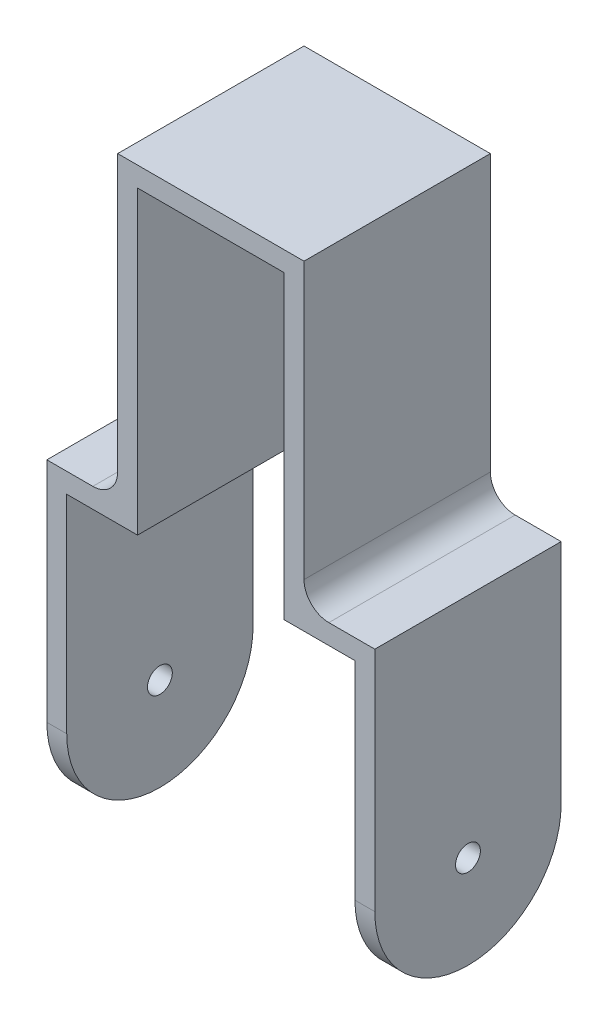
SolidWorks part; units mm, degrees
ref_plane "Front Plane" through (0, 0, 0) normal (0, 0, 1) x (1, 0, 0)
ref_plane "Top Plane" through (0, 0, 0) normal (0, 1, 0) x (1, 0, 0)
ref_plane "Right Plane" through (0, 0, 0) normal (1, 0, 0) x (0, 0, -1)
sketch "Sketch1" plane through (0, 0, 0) normal (0, 0, 1) x (1, 0, 0)
  line L0 (8, -8) -> (8, -129)
  line L1 (0, 0) -> (8, 0)
  line L2 (0, 0) -> (0, -121)
  line L4 (75, 0) -> (75, -121)
  line L5 (67, -8) -> (67, -129)
  line L6 (67, 0) -> (75, 0)
  line L8 (0, -121) -> (-28.5, -121)
  line L10 (8, -117) -> (8, -125)
  line L12 (67, -117) -> (67, -129)
  line L14 (8, -121) -> (8, -129)
  line L16 (67, -121) -> (67, -129)
  line L17 (75, 0) -> (0, 0)
  line L18 (75, 0) -> (75, -8)
  line L19 (67, -8) -> (8, -8)
  line L20 (0, 0) -> (0, -8)
  line L21 (103.5, -121) -> (75, -121)
  line L22 (103.5, -121) -> (103.5, -250)
  line L23 (103.5, -250) -> (95.5, -250)
  line L24 (-28.5, -121) -> (-28.5, -250)
  line L25 (95.5, -129) -> (67, -129)
  line L26 (95.5, -129) -> (95.5, -250)
  line L28 (-20.5, -129) -> (-20.5, -250)
  line L29 (8, -129) -> (-20.5, -129)
  line L31 (-20.5, -250) -> (-28.5, -250)
  dimension "D1" = 75
  dimension "D3" = 8
  dimension "D4" = 8
  dimension "D7" = 8
  dimension "D8" = 132
  dimension "D9" = 28.5
  dimension "D10" = 8
  dimension "D11" = 8
extrude "Boss-Extrude2" add sketch "Sketch1" along normal blind 75 contours L0 L5 L12 L10 | L5 L12 L4 L6 | L2 L0 L10 L1 region at (5.1729, -62.5, 0)
sketch "Sketch2" plane through (0, 0, 0) normal (1, 0, 0) x (0, 0, -1)
  line L0 (-75, -250) -> (0, -250) construction
  line L1 (-75, -121) -> (-75, -250) construction
  circle A0 centre (-37.5, -212.5) radius 5
  point P4 (-37.5, -250)
  dimension "D1" = 10
  dimension "D2" = 37.5
  dimension "D3" = 37.5
extrude "Cut-Extrude1" cut sketch "Sketch2" against normal blind 47 and the other way blind 148
fillet "Fillet1" radius 37.5 4 edges at (-24.5, -250, 75) (-24.5, -250, 0) (99.5, -250, 75) (99.5, -250, 0)
fillet "Fillet2" radius 10 2 edges at (0, -121, 37.5) (75, -121, 37.5)
